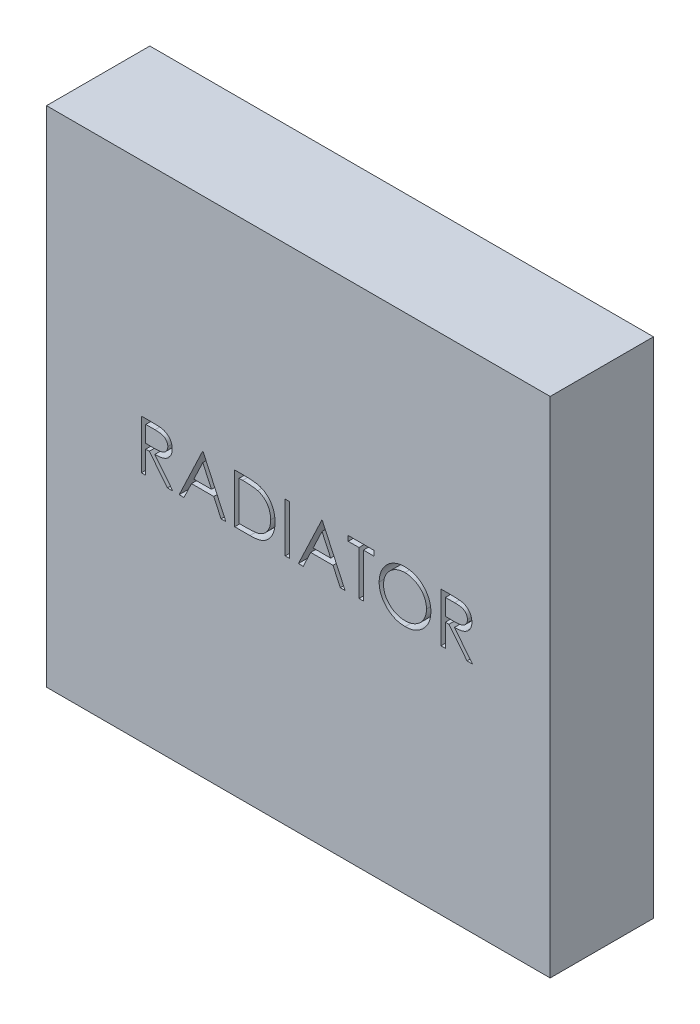
SolidWorks part; units mm, degrees
ref_plane "정면" through (0, 0, 0) normal (0, 0, 1) x (1, 0, 0)
ref_plane "윗면" through (0, 0, 0) normal (0, 1, 0) x (1, 0, 0)
ref_plane "우측면" through (0, 0, 0) normal (1, 0, 0) x (0, 0, -1)
sketch "Sketch1" plane through (0, 0, 0) normal (0, 1, 0) x (1, 0, 0)
  line L1 (-97.5, -20) -> (97.5, -20)
  line L2 (-97.5, -20) -> (-97.5, 20)
  line L3 (-97.5, 20) -> (97.5, 20)
  line L4 (97.5, -20) -> (97.5, 20)
  line L5 (-97.5, -20) -> (97.5, 20) construction
  line L6 (-97.5, 20) -> (97.5, -20) construction
  point P0 (0, 0)
  dimension "D1" = 40
  dimension "D2" = 195
extrude "Boss-Extrude1" add sketch "Sketch1" along normal blind 97.5 and the other way blind 97.5
sketch "Sketch2" plane through (0, 0, 20) normal (0, 0, 1) x (1, 0, 0)
  text T0 "RADIATOR" font "Century Gothic" height in points 72
extrude "Cut-Extrude1" cut sketch "Sketch2" against normal blind 15
